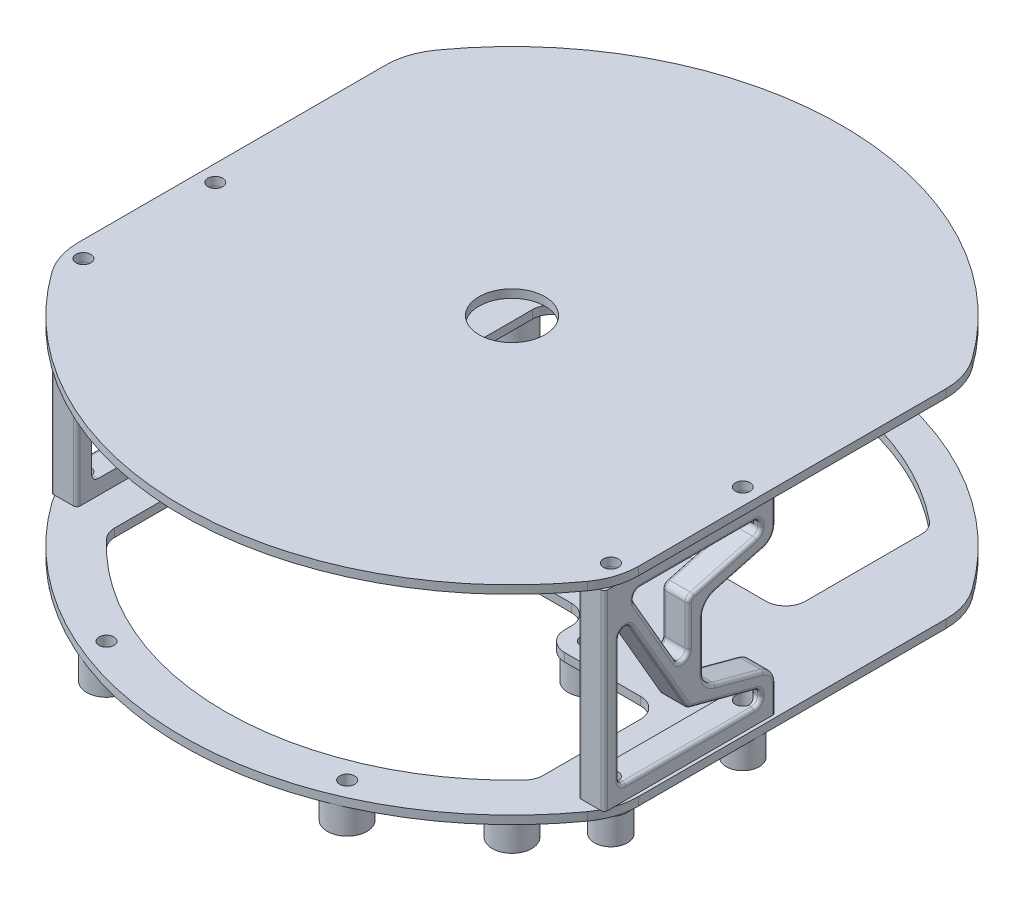
SolidWorks part; units mm, degrees
ref_plane "Front" through (0, 0, 0) normal (0, 0, 1) x (1, 0, 0)
ref_plane "Top" through (0, 0, 0) normal (0, 1, 0) x (1, 0, 0)
ref_plane "Right" through (0, 0, 0) normal (1, 0, 0) x (0, 0, -1)
sketch "Sketch1" plane through (0, 0, 0) normal (0, 1, 0) x (1, 0, 0)
  line L0 (0, 71.1393) -> (0, -87.7098) construction
  line L1 (-42.5, 26.3391) -> (-42.5, -26.3391)
  line L2 (42.5, 26.3391) -> (42.5, -26.3391)
  arc A0 (-42.5, -26.3391) -> (42.5, -26.3391) centre (0, 0) ccw
  arc A1 (42.5, 26.3391) -> (-42.5, 26.3391) centre (0, 0) ccw
  dimension "D1" = 100
  dimension "D2" = 85
extrude "Boss-Extrude1" add sketch "Sketch1" along normal blind 1.25
sketch "Sketch2" plane through (0, 0, 0) normal (0, -1, 0) x (1, 0, 0)
  line L0 (0, 45.5144) -> (0, -63.1722) construction
  line L1 (-51.2989, 0) -> (55.2567, 0) construction
  circle A0 centre (-33, 33) radius 3
  circle A2 centre (-33, 33) radius 1.125
  circle A4 centre (-33, -33) radius 1.125
  circle A5 centre (-33, -33) radius 3
  circle A6 centre (33, -33) radius 3
  circle A7 centre (33, -33) radius 1.125
  circle A8 centre (33, 33) radius 1.125
  circle A9 centre (33, 33) radius 3
  dimension "D3" = 2.25
  dimension "D4" = 6
  dimension "D1" = 66
  dimension "D2" = 66
extrude "Boss-Extrude2" add sketch "Sketch2" along normal blind 4
fillet "Fillet1" radius 10 4 edges at (-42.5, 0.625, -26.3391) (-42.5, 0.625, 26.3391) (42.5, 0.625, -26.3391) (42.5, 0.625, 26.3391)
sketch "Sketch3" plane through (0, 1.25, 0) normal (0, 1, 0) x (1, 0, 0)
  line L0 (0, 58.0627) -> (0, -62.1815) construction
  line L1 (-18.25, -6.75) -> (18.25, -6.75) construction
  line L2 (-18.25, -6.75) -> (-18.25, -43.25) construction
  line L3 (-18.25, -43.25) -> (18.25, -43.25) construction
  line L4 (18.25, -6.75) -> (18.25, -43.25) construction
  line L5 (-18.25, -6.75) -> (18.25, -43.25) construction
  line L6 (-18.25, -43.25) -> (18.25, -6.75) construction
  circle A0 centre (-18.25, -6.75) radius 1.125
  circle A1 centre (18.25, -6.75) radius 1.125
  circle A2 centre (18.25, -43.25) radius 1.125
  circle A3 centre (-18.25, -43.25) radius 1.125
  circle A4 centre (-40, -5) radius 1.125
  circle A5 centre (-40, -25) radius 1.125
  circle A6 centre (40, -25) radius 1.125
  circle A7 centre (40, -5) radius 1.125
  point P0 (0, -25)
  dimension "D1" = 2.25
  dimension "D2" = 36.5
  dimension "D3" = 25
  dimension "D4" = 20
  dimension "D5" = 80
  dimension "D6" = 0
sketch "Sketch4" plane through (0, 0, 0) normal (0, -1, 0) x (1, 0, 0)
  circle A0 centre (-18.25, 43.25) radius 3
  circle A1 centre (18.25, 43.25) radius 3
  circle A2 centre (18.25, 6.75) radius 3
  circle A3 centre (-18.25, 6.75) radius 3
  circle A4 centre (-40, 25) radius 2.5
  circle A5 centre (-40, 5) radius 2.5
  circle A6 centre (40, 25) radius 2.5
  circle A7 centre (40, 5) radius 2.5
  dimension "D1" = 6
  dimension "D2" = 5
extrude "Boss-Extrude3" add sketch "Sketch4" along normal up to surface (4 mm away) up to face at (-33, -4, 30)
extrude "Cut-Extrude1" cut sketch "Sketch3" against normal through all
sketch "Sketch6" plane through (0, 0, 0) normal (0, -1, 0) x (1, 0, 0)
  line L0 (-29.5, -33.9816) -> (-29.5, -12)
  line L1 (-29.5, -12) -> (-6, -12)
  line L2 (29.5, -12) -> (29.5, -33.9816)
  line L3 (0, 0) -> (0, -57.2909) construction
  line L4 (-32.5, 28.9137) -> (-32.5, 10)
  line L5 (-32.5, 10) -> (-15, 10)
  line L6 (32.5, 10) -> (32.5, 28.9137)
  line L7 (-6, -12) -> (-6, -44.5982)
  line L8 (6, -12) -> (6, -44.5982)
  line L9 (6, -12) -> (29.5, -12)
  line L10 (15, 10) -> (32.5, 10)
  line L12 (-15, 10) -> (-15, 3)
  line L13 (-15, 3) -> (15, 3)
  line L14 (15, 10) -> (15, 3)
  arc A0 (-29.5, -33.9816) -> (-6, -44.5982) centre (0, 0) ccw
  arc A1 (-40.625, -29.1481) -> (40.625, -29.1481) centre (0, 0) ccw construction
  arc A2 (-32.5, 28.9137) -> (32.5, 28.9137) centre (0, 0) cw
  arc A3 (40.625, 29.1481) -> (-40.625, 29.1481) centre (0, 0) ccw construction
  arc A4 (6, -44.5982) -> (29.5, -33.9816) centre (0, 0) ccw
  dimension "D2" = 5
  dimension "D4" = 6.5
  dimension "D1" = 59
  dimension "D3" = 12
  dimension "D5" = 10
  dimension "D6" = 12
  dimension "D7" = 65
  dimension "D8" = 7
  dimension "D9" = 30
extrude "Cut-Extrude2" cut sketch "Sketch6" against normal through all
fillet "Fillet2" radius 3 16 edges at (-29.5, 0.625, -12) (-6, 0.625, -12) (-6, 0.625, -44.5982) (29.5, 0.625, -12) (29.5, 0.625, -33.9816) (6, 0.625, -44.5982) (6, 0.625, -12) (-29.5, 0.625, -33.9816) (32.5, 0.625, 28.9137) (-32.5, 0.625, 28.9137) (-32.5, 0.625, 10) (32.5, 0.625, 10) (15, 0.625, 3) (15, 0.625, 10) (-15, 0.625, 3) (-15, 0.625, 10)
ref_point "Point1"
ref_plane "Plane1" through (-40, 0, 0) normal (-1, 0, 0) x (0, 0, 1)
sketch "Sketch7" plane through (-40, 0, 0) normal (-1, 0, 0) x (0, 0, 1)
  line L0 (2, 1.25) -> (2, 7.25)
  line L1 (-23.3184, 1.25) -> (23.3184, 1.25) construction
  line L2 (2, 7.25) -> (13, 10.1974)
  line L3 (13, 10.1974) -> (13, 21.3026)
  line L4 (13, 21.3026) -> (2, 24.25)
  line L5 (2, 24.25) -> (2, 30.25)
  line L6 (2, 30.25) -> (28, 30.25)
  line L7 (28, 30.25) -> (28, 1.25)
  line L8 (28, 1.25) -> (2, 1.25)
  line L9 (4.25, 28) -> (24.2157, 28)
  line L11 (25.75, 3.5) -> (4.25, 3.5)
  line L12 (4.25, 3.5) -> (4.25, 5.5235)
  line L13 (4.25, 5.5235) -> (15.25, 8.471)
  line L14 (15.25, 12.471) -> (15.25, 23.029)
  line L15 (15.25, 23.029) -> (4.25, 25.9765)
  line L16 (4.25, 25.9765) -> (4.25, 28)
  line L17 (15.25, 8.471) -> (25.75, 26.6575)
  line L19 (24.2157, 28) -> (15.25, 12.471)
  line L21 (15.25, 8.471) -> (15.25, 23.029) construction
  line L22 (25.75, 26.6575) -> (25.75, 3.5)
  line L23 (25.75, 28) -> (25.75, 3.5) construction
  line L24 (4.25, 28) -> (25.75, 28) construction
  dimension "D1" = 2
  dimension "D2" = 26
  dimension "D3" = 15
  dimension "D4" = 15
  dimension "D5" = 15
  dimension "D6" = 6
  dimension "D7" = 29
  dimension "D9" = 2
  dimension "D10" = 30
  dimension "D8" = 2.25
extrude "Boss-Extrude4" add sketch "Sketch7" along normal mid plane 4 separate body
fillet "Fillet3" radius 2.5 4 edges at (-40, 7.25, 2) (-40, 10.1974, 13) (-40, 21.3026, 13) (-40, 24.25, 2)
fillet "Fillet4" radius 1 10 edges at (-40, 26.6575, 25.75) (-40, 8.471, 15.25) (-40, 5.5235, 4.25) (-40, 3.5, 25.75) (-40, 3.5, 4.25) (-40, 12.471, 15.25) (-40, 28, 4.25) (-40, 25.9765, 4.25) (-40, 23.029, 15.25) (-40, 28, 24.2157)
fillet "Fillet5" radius 0.5 50 edges at (-38, 15.75, 28) (-38, 3.2908, 2) (-38, 6.8536, 2.5166) (-38, 8.7237, 7.5) (-38, 10.5939, 12.4834) (-38, 15.75, 13) (-38, 20.9061, 12.4834) (-38, 22.7763, 7.5) (-38, 24.6464, 2.5166) (-38, 28.2092, 2) (-42, 3.2908, 2) (-42, 6.8536, 2.5166) (-42, 8.7237, 7.5) (-42, 10.5939, 12.4834) (-42, 15.75, 13) (-42, 20.9061, 12.4834) (-42, 22.7763, 7.5) (-42, 24.6464, 2.5166) (-42, 28.2092, 2) (-42, 15.75, 28) (-42, 3.7929, 4.5429) (-42, 5.3649, 4.4566) (-42, 7.0429, 9.9205) (-42, 8.5363, 15.1998) (-42, 16.1276, 19.6705) (-42, 23.8914, 25.0088) (-42, 13.7127, 25.75) (-42, 3.7929, 25.4571) (-42, 3.5, 15) (-38, 27.7071, 4.5429) (-42, 27.7071, 4.5429) (-38, 26.1351, 4.4566) (-38, 24.5028, 9.75) (-38, 22.8705, 15.0434) (-38, 19.2324, 15.25) (-38, 15.2371, 15.9912) (-42, 26.1351, 4.4566) (-42, 24.5028, 9.75) (-42, 22.8705, 15.0434) (-42, 19.2324, 15.25) (-42, 15.2371, 15.9912) (-38, 28, 13.8668) (-42, 28, 13.8668) (-38, 21.1015, 20.2328) (-42, 21.1015, 20.2328) (-38, 27.5, 23.3497) (-42, 27.5, 23.3497) (-38, 26.8719, 4.25) (-42, 26.8719, 4.25) (-42, 4.6281, 4.25)
sketch "Sketch8" plane through (0, 1.25, 0) normal (0, -1, 0) x (1, 0, 0)
  circle A0 centre (-40, 5) radius 1.125 construction
  circle A1 centre (-40, 25) radius 1.125 construction
  circle A2 centre (-40, 5) radius 1.125
  circle A3 centre (-40, 25) radius 1.125
extrude "Cut-Extrude3" cut sketch "Sketch8" against normal blind 3.5
extrude "Cut-Extrude4" cut sketch "Sketch8<3>" along normal blind 3.5 from surface starting at face at (-40, 30.25, 15)
sketch "Sketch8<3>" plane through (0, 1.25, 0) normal (0, -1, 0) x (1, 0, 0) same geometry as "Sketch8"
mirror "Mirror1" about plane through (0, 0, 0) normal (1, 0, 0) of bodies 109
sketch "Sketch9" plane through (0, 30.25, 0) normal (0, 1, 0) x (1, 0, 0)
  line L0 (-42.5, 23.3184) -> (-42.5, -23.3184) construction
  line L1 (42.5, -23.3184) -> (42.5, 23.3184) construction
  line L2 (-42.5, 23.3184) -> (-42.5, -23.3184)
  line L3 (42.5, -23.3184) -> (42.5, 23.3184)
  arc A0 (40.625, 29.1481) -> (-40.625, 29.1481) centre (0, 0) ccw construction
  arc A1 (-40.625, 29.1481) -> (-42.5, 23.3184) centre (-32.5, 23.3184) ccw construction
  arc A2 (-42.5, -23.3184) -> (-40.625, -29.1481) centre (-32.5, -23.3184) ccw construction
  arc A3 (-40.625, -29.1481) -> (40.625, -29.1481) centre (0, 0) ccw construction
  arc A4 (40.625, -29.1481) -> (42.5, -23.3184) centre (32.5, -23.3184) ccw construction
  arc A5 (42.5, 23.3184) -> (40.625, 29.1481) centre (32.5, 23.3184) ccw construction
  arc A6 (-40.625, 29.1481) -> (-42.5, 23.3184) centre (-32.5, 23.3184) ccw
  arc A7 (-42.5, -23.3184) -> (-40.625, -29.1481) centre (-32.5, -23.3184) ccw
  arc A8 (-40.625, -29.1481) -> (40.625, -29.1481) centre (0, 0) ccw
  arc A9 (40.625, -29.1481) -> (42.5, -23.3184) centre (32.5, -23.3184) ccw
  arc A10 (42.5, 23.3184) -> (40.625, 29.1481) centre (32.5, 23.3184) ccw
  arc A11 (40.625, 29.1481) -> (-40.625, 29.1481) centre (0, 0) ccw
  circle A12 centre (0, 0) radius 5
  dimension "D1" = 10
extrude "Boss-Extrude6" add sketch "Sketch9" along normal blind 1.25 separate body
sketch "Sketch10" plane through (0, 30.25, 0) normal (0, -1, 0) x (1, 0, 0)
  line L0 (0, 53.912) -> (0, -58.3807) construction
  circle A0 centre (-40, 5) radius 1.125 construction
  circle A1 centre (-40, 25) radius 1.125 construction
  circle A2 centre (-40, 5) radius 1.125
  circle A3 centre (-40, 25) radius 1.125
  circle A4 centre (40, 25) radius 1.125
  circle A5 centre (40, 5) radius 1.125
extrude "Cut-Extrude5" cut sketch "Sketch10" against normal through all
sketch "Sketch11" plane through (0, 31.5, 0) normal (0, 1, 0) x (1, 0, 0)
  line L0 (0, 0) -> (0, 40) construction
  line L1 (0, 40) -> (-30.3109, 22.5) construction
  line L2 (0, 40) -> (30.3109, 22.5) construction
  circle A0 centre (0, 40) radius 1.5
  circle A1 centre (-15.1554, 31.25) radius 1.5
  circle A2 centre (-30.3109, 22.5) radius 1.5
  circle A3 centre (15.1554, 31.25) radius 1.5
  circle A4 centre (30.3109, 22.5) radius 1.5
  circle A5 centre (0, -25) radius 1.5
  point P14 (0, 0)
  dimension "D4" = 3
  dimension "D1" = 120
  dimension "D2" = 40
  dimension "D3" = 35
  dimension "D5" = 25
extrude "Cut-Extrude6" [suppressed] cut sketch "Sketch11" against normal up to next
equation "\"D5@Sketch7\"=\"D4@Sketch7\""
